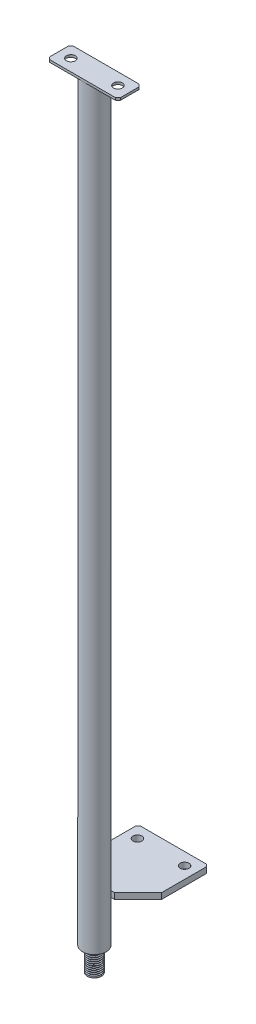
SolidWorks part; units mm, degrees
ref_plane "Front Plane" through (0, 0, 0) normal (0, 0, 1) x (1, 0, 0)
ref_plane "Top Plane" through (0, 0, 0) normal (0, 1, 0) x (1, 0, 0)
ref_plane "Right Plane" through (0, 0, 0) normal (1, 0, 0) x (0, 0, -1)
sketch "Sketch1" plane through (0, 0, 0) normal (0, 1, 0) x (1, 0, 0)
  line L0 (-7.62, 0) -> (-12.7, 0) construction
  circle A0 centre (0, 0) radius 12.7
  circle A1 centre (0, 0) radius 7.62
  dimension "D1" = 25.4
  dimension "D2" = 5.08
extrude "Boss-Extrude1" add sketch "Sketch1" along normal blind 812.8
ref_plane "Plane1" through (0, 12.7, 0) normal (0, -1, 0) x (-1, 0, 0)
sketch "Sketch2" plane through (0, 12.7, 0) normal (0, -1, 0) x (-1, 0, 0)
  circle A0 centre (0, 0) radius 7.62
extrude "Boss-Extrude2" add sketch "Sketch2" along normal blind 38.1
sketch "Sketch5" plane through (0, -25.4, 0) normal (0, -1, 0) x (1, 0, 0)
  circle A0 centre (0, 0) radius 7.62
thread "Thread1" pitch 1.9538 method cut profile "Thread Profile2" start angle 0, offset 0, length 38.1, pitch 1.9538, diameter 15.24
ref_plane "Plane3" through (7.62, -25.4, 0) normal (0, 0, 1) x (1, 0, 0)
sketch "Thread Profile2" plane through (7.62, -25.4, 0) normal (0, 0, 1) x (1, 0, 0)
  line L0 (0, 0) -> (0, 1.9538) construction
  line L11 (0, 0) -> (0, 1.7096)
  line L12 (0, 1.7096) -> (-1.0576, 1.099)
  line L13 (-1.0576, 1.099) -> (-1.0576, 0.6106)
  line L15 (-1.0576, 0.6106) -> (0, 0)
  line L17 (-1.0576, 0.8548) -> (0, 0.8548) construction
  point P2 (0, 0)
  dimension "Pitch" = 1.9538
  dimension "Profile_Angle" = 60
  dimension "Profile_Land" = 0.4885
  dimension "Profile_Height" = 1.0576
ref_plane "Plane4" through (0, 0, 12.7) normal (0, 0, 1) x (1, 0, 0)
ref_plane "Plane5" through (0, 50.8, 0) normal (0, -1, 0) x (-1, 0, 0)
sketch "Sketch10" plane through (0, 50.8, 0) normal (0, -1, 0) x (-1, 0, 0)
  line L0 (0, 0) -> (0, 12.7) construction
  line L1 (-8.9803, 8.9803) -> (0, 0) construction
  line L2 (0, 0) -> (8.9803, 8.9803) construction
  line L3 (-8.9803, 8.9803) -> (-12.7, 8.9803)
  line L4 (-12.7, 8.9803) -> (-38.1, 34.3803)
  line L5 (-38.1, 34.3803) -> (-38.1, 85.1803)
  line L6 (-38.1, 85.1803) -> (38.1, 85.1803)
  line L7 (0, 85.1803) -> (0, 12.7) construction
  line L8 (0, 0) -> (-8.9803, 8.9803) construction
  line L9 (8.9803, 8.9803) -> (0, 0) construction
  line L10 (38.1, 34.3803) -> (38.1, 85.1803)
  line L11 (12.7, 8.9803) -> (38.1, 34.3803)
  line L12 (8.9803, 8.9803) -> (12.7, 8.9803)
  arc A0 (-8.9803, 8.9803) -> (8.9803, 8.9803) centre (0, 0) cw
  circle A1 centre (0, 0) radius 12.7 construction
  dimension "D1" = 45
  dimension "D3" = 76.2
  dimension "D4" = 38.1
  dimension "D5" = 25.4
  dimension "D6" = 25.4
extrude "Boss-Extrude4" add sketch "Sketch10" along normal blind 6.35
sketch "Sketch11" plane through (0, 50.8, 0) normal (0, 1, 0) x (1, 0, 0)
  line L0 (0, 0) -> (0, 71.842) construction
  line L1 (0, 71.842) -> (-25.4, 71.842) construction
  circle A0 centre (-25.4, 71.842) radius 4.7625
  circle A1 centre (25.4, 71.842) radius 4.7625
  dimension "D1" = 9.525
  dimension "D2" = 76.2
  dimension "D3" = 25.4
extrude "Cut-Extrude2" cut sketch "Sketch11" against normal up to next
sketch "Sketch12" plane through (0, 812.8, 0) normal (0, 1, 0) x (1, 0, 0)
  line L1 (38.1, -12.7) -> (-38.1, -12.7)
  line L2 (38.1, -12.7) -> (38.1, 12.7)
  line L3 (38.1, 12.7) -> (-38.1, 12.7)
  line L4 (-38.1, -12.7) -> (-38.1, 12.7)
  line L5 (38.1, -12.7) -> (-38.1, 12.7) construction
  line L6 (38.1, 12.7) -> (-38.1, -12.7) construction
  point P0 (0, 0)
  point P5 (0, 0)
  point P9 (-27.2078, 0)
  dimension "D1" = 25.4
  dimension "D2" = 76.2
extrude "Boss-Extrude5" add sketch "Sketch12" along normal blind 2.54
sketch "Sketch13" plane through (0, 815.34, 0) normal (0, 1, 0) x (1, 0, 0)
  line L0 (0, 0) -> (-25.4, 0) construction
  line L1 (0, 0) -> (0, 12.7) construction
  line L2 (38.1, 12.7) -> (-38.1, 12.7) construction
  circle A0 centre (-25.4, 0) radius 4.7625
  circle A1 centre (25.4, 0) radius 4.7625
  dimension "D1" = 9.525
  dimension "D2" = 25.4
extrude "Cut-Extrude3" cut sketch "Sketch13" against normal up to next
chamfer "Chamfer1" distance 2.54 angle 45 6 edges at (38.1, 814.07, 12.7) (38.1, 814.07, -12.7) (-38.1, 814.07, 12.7) (-38.1, 814.07, -12.7) (38.1, 47.625, -85.1803) (-38.1, 47.625, -85.1803)
